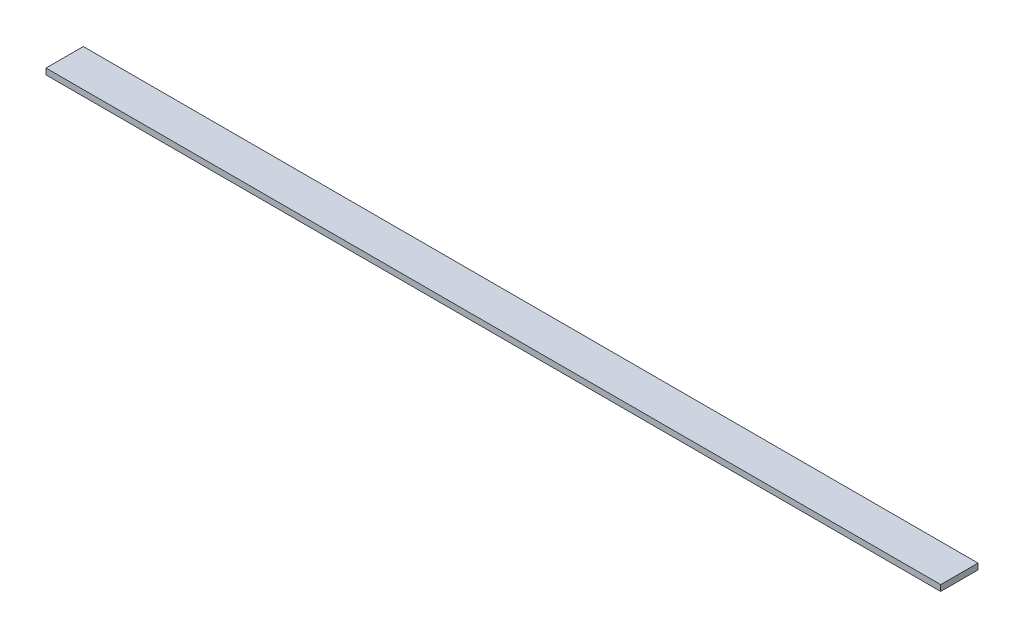
SolidWorks part; units mm, degrees
ref_plane "Спереди" through (0, 0, 0) normal (0, 0, 1) x (1, 0, 0)
ref_plane "Сверху" through (0, 0, 0) normal (0, 1, 0) x (1, 0, 0)
ref_plane "Справа" through (0, 0, 0) normal (1, 0, 0) x (0, 0, -1)
sketch "Эскиз1" plane through (0, 0, 0) normal (0, 1, 0) x (1, 0, 0)
  line L1 (-600, 25) -> (600, 25)
  line L2 (-600, 25) -> (-600, -25)
  line L3 (-600, -25) -> (600, -25)
  line L4 (600, 25) -> (600, -25)
  line L5 (-600, 25) -> (600, -25) construction
  line L6 (-600, -25) -> (600, 25) construction
  point P0 (0, 0)
extrude "Бобышка-Вытянуть1" add sketch "Эскиз1" along normal blind 8
